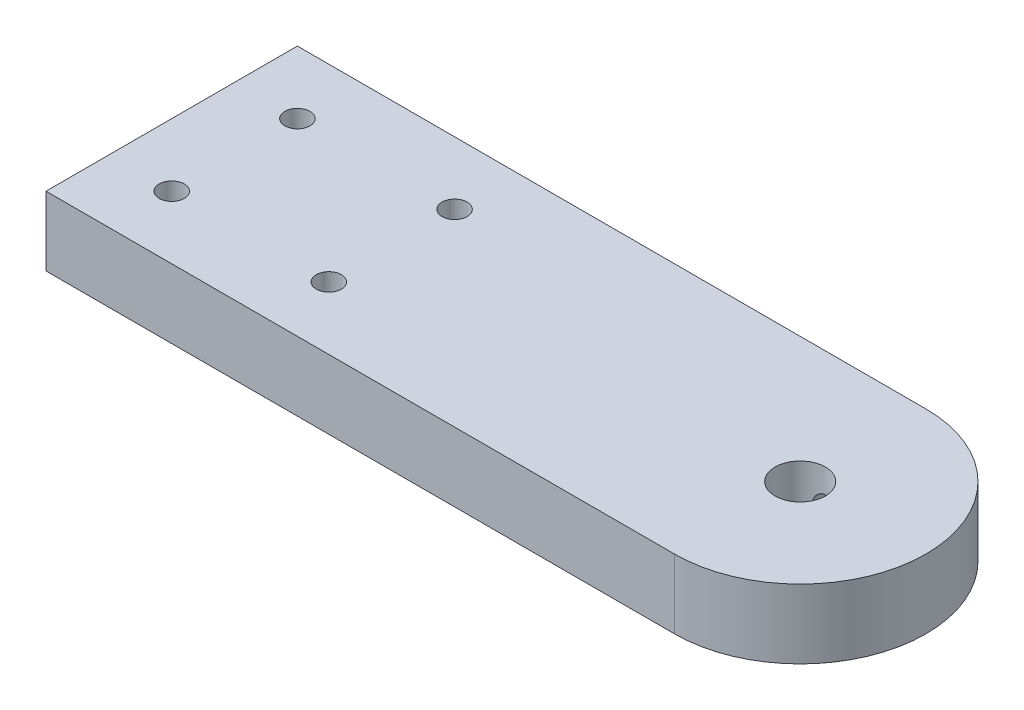
SolidWorks part; units mm, degrees
material "1060 Alloy"
ref_plane "Front Plane" through (0, 0, 0) normal (0, 0, 1) x (1, 0, 0)
ref_plane "Top Plane" through (0, 0, 0) normal (0, 1, 0) x (1, 0, 0)
ref_plane "Right Plane" through (0, 0, 0) normal (1, 0, 0) x (0, 0, -1)
sketch "Sketch1" plane through (0, 0, 0) normal (0, 1, 0) x (1, 0, 0)
  line L0 (-100, 20) -> (20, 20)
  line L1 (20, 20) -> (20, -5)
  line L2 (20, -5) -> (-100, -5) construction
  line L3 (-100, -5) -> (-100, 20)
  line L4 (20, -5) -> (20, -20)
  line L5 (20, -20) -> (-100, -20)
  line L6 (-100, -20) -> (-100, -5)
  line L7 (20, -10) -> (-90, -10) construction
  line L8 (-90, -10) -> (-90, -5) construction
  line L9 (-90, -5) -> (-90, 10) construction
  line L10 (-90, 10) -> (20, 10) construction
  circle A0 centre (0, 0) radius 4
  circle A1 centre (-90, 10) radius 2
  circle A2 centre (-65, 10) radius 2
  circle A3 centre (-65, -10) radius 2
  circle A4 centre (-90, -10) radius 2
  arc A5 (0, -20) -> (0, 20) centre (0, 0) ccw
  dimension "D1" = 8
  dimension "D7" = 4
  dimension "D2" = 20
  dimension "D3" = 25
  dimension "D4" = 20
  dimension "D5" = 15
  dimension "D6" = 120
  dimension "D9" = 25
  dimension "D8" = 10
extrude "Boss-Extrude1" add sketch "Sketch1" along normal blind 11 contours L5 A5 L0 L3 L6 A4 A3 A2 A1 A0 region at (-42.1334, 0, 0)
hole_wizard "M4 Tapped Hole1" positions "Sketch2" profile "Sketch3" tap size "M4" standard "ISO"
sketch "Sketch2" plane through (0, 0, -20) normal (0, 0, -1) x (-1, 0, 0)
  line L0 (0, 55) -> (0, -55) construction
  line L1 (0, 11) -> (0, 0) construction
  point P0 (0, 5.5)
  point P11 (0, 5.5)
sketch "Sketch3" plane through (0, 5.5, -20) normal (1, 0, 0) x (0, 1, 0)
  line L0 (0, 0) -> (0, 20.9914)
  line L1 (0, 20.9914) -> (1.65, 20)
  line L2 (1.65, 20) -> (1.65, 0)
  line L5 (1.65, 0) -> (0, 0)
  line L10 (0, 20.9914) -> (-1.65, 20) construction
  line L11 (0, -6.35) -> (0, 107.95) construction
  dimension "Tap Drill Dia." = 3.3
  dimension "Tap Drill Depth" = 20
  dimension "Drill Angle" = 118
cosmetic thread "Hole Thread1" parameters "D1"=8, "D2"=4
